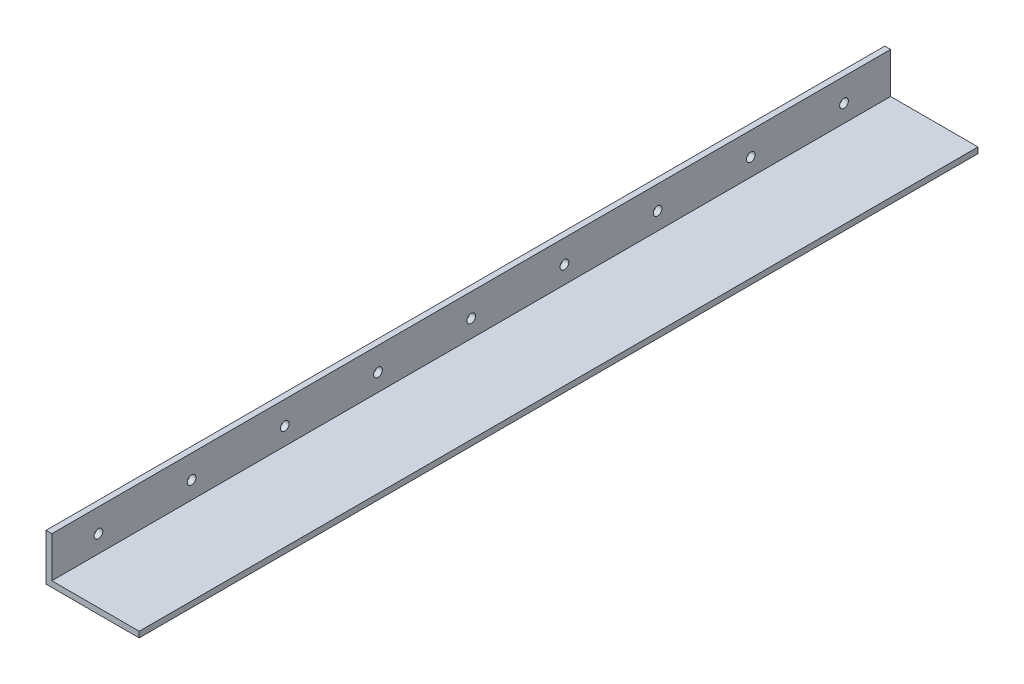
SolidWorks part; units mm, degrees
ref_plane "Front Plane" through (0, 0, 0) normal (0, 0, 1) x (1, 0, 0)
ref_plane "Top Plane" through (0, 0, 0) normal (0, 1, 0) x (1, 0, 0)
ref_plane "Right Plane" through (0, 0, 0) normal (1, 0, 0) x (0, 0, -1)
sketch "Sketch1" plane through (0, 0, 0) normal (0, 0, 1) x (1, 0, 0)
  line L1 (0, 0) -> (50.8, 0)
  line L2 (0, 0) -> (0, 25.4)
  line L3 (0, 25.4) -> (50.8, 25.4)
  line L4 (50.8, 0) -> (50.8, 25.4)
  line L5 (50.8, 25.4) -> (3.175, 25.4)
  line L6 (50.8, 25.4) -> (50.8, 3.175)
  line L7 (50.8, 3.175) -> (3.175, 3.175)
  line L8 (3.175, 25.4) -> (3.175, 3.175)
  dimension "D1" = 3.175
  dimension "D2" = 3.175
  dimension "D3" = 25.4
  dimension "D4" = 50.8
extrude "Boss-Extrude1" add sketch "Sketch1" along normal blind 457.2 contours L8 L3 L2 L1 L4 L7 region at (0.568, 12.7, 0)
sketch "Sketch2" plane through (0, 0, 0) normal (-1, 0, 0) x (0, 0, 1)
  line L0 (457.2, 0) -> (0, 0) construction
  line L1 (457.2, 0) -> (457.2, 25.4) construction
  circle A0 centre (431.8, 12.7) radius 2.3813
  circle A1 centre (381, 12.7) radius 2.3813
  circle A2 centre (330.2, 12.7) radius 2.3813
  circle A3 centre (279.4, 12.7) radius 2.3813
  circle A4 centre (228.6, 12.7) radius 2.3813
  circle A5 centre (177.8, 12.7) radius 2.3813
  circle A6 centre (127, 12.7) radius 2.3813
  circle A7 centre (76.2, 12.7) radius 2.3813
  circle A8 centre (25.4, 12.7) radius 2.3813
  circle A9 centre (-25.4, 12.7) radius 2.3813
  dimension "D3" = 4.7625
  dimension "D1" = 12.7
  dimension "D2" = 25.4
  dimension "D4" = 10
extrude "Cut-Extrude1" cut sketch "Sketch2" against normal through all
